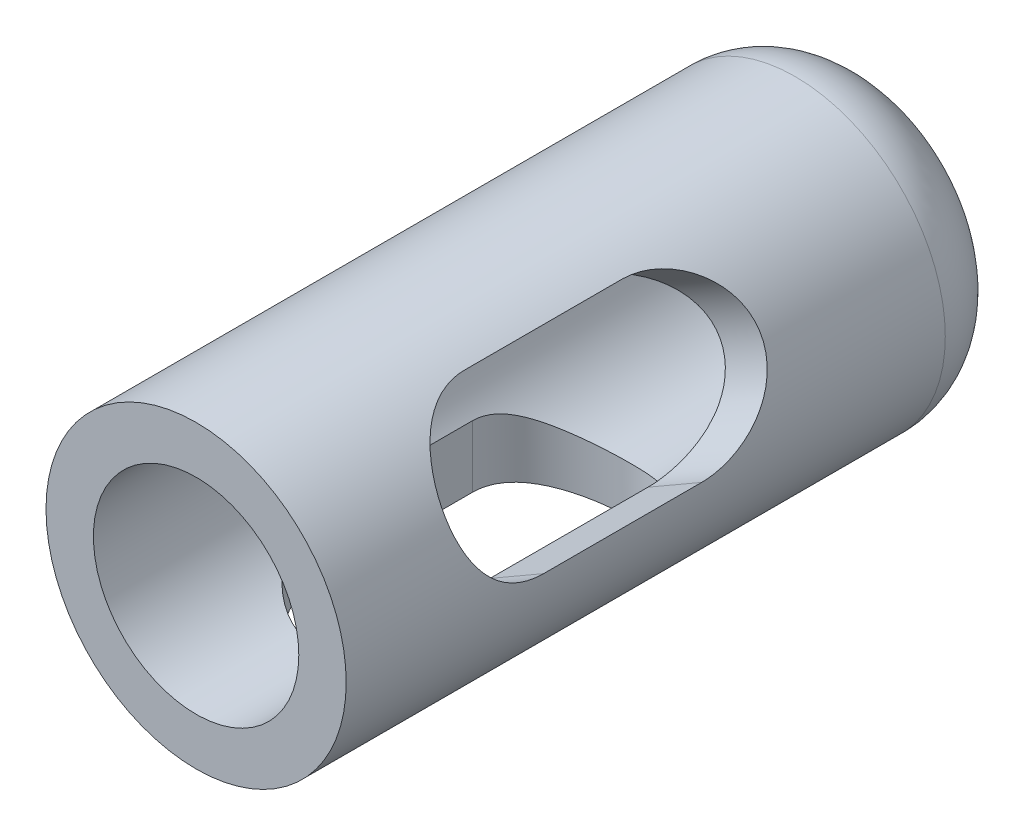
SolidWorks part; units mm, degrees
ref_plane "정면" through (0, 0, 0) normal (0, 0, 1) x (1, 0, 0)
ref_plane "윗면" through (0, 0, 0) normal (0, 1, 0) x (1, 0, 0)
ref_plane "우측면" through (0, 0, 0) normal (1, 0, 0) x (0, 0, -1)
sketch "스케치1" plane through (0, 0, 0) normal (0, 0, 1) x (1, 0, 0)
  circle A0 centre (0, 0) radius 3.8
  circle A1 centre (0, 0) radius 2.6
  dimension "D1" = 7.6
  dimension "D2" = 5.2
extrude "보스-돌출1" add sketch "스케치1" along normal blind 17
sketch "스케치2" plane through (0, 0, 0) normal (0, 1, 0) x (1, 0, 0)
  line L0 (0, -17.6377) -> (0, 0) construction
  line L1 (-2.6, -17) -> (2.6, -17) construction
  line L2 (-2.6, -17) -> (2.6, -17)
  line L3 (-3.8, -17) -> (-2.6, -17)
  line L4 (2.6, -17) -> (3.8, -17)
  line L5 (2.6, -17) -> (3.8, -17)
  line L6 (-3.8, -17) -> (-2.6, -17)
  line L7 (-2, -8) -> (-2, -12)
  line L8 (-2, -12) -> (2, -12)
  line L9 (2, -12) -> (2, -8)
  circle A0 centre (0, -12) radius 2
  circle A1 centre (0, -8) radius 2
  dimension "D1" = 4
  dimension "D3" = 4
  dimension "D2" = 5
  dimension "D4" = 4
extrude "컷-돌출1" cut sketch "스케치2" against normal blind 17 contours L0 A0 A1 L9 | A0 L0 A1 L7 | A1 A0 L9 | L0 L8 A0 A1 | L8 L0 A1 A0 | A1 L7 A0 | A0 L0 L8 | L0 A0 L8 | L0 A1 A0 | A1 L0 A0 region at (-0.8488, 0, 12.8488) region at (0.8488, 0, 12.8488) region at (-0.8488, 0, 11.1512) region at (0.8488, 0, 11.1512) region at (-1.5533, 0, 10) region at (1.5533, 0, 10) region at (-0.8488, 0, 8) region at (0.8488, 0, 8)
sketch "스케치3" plane through (0, 0, 0) normal (0, 0, 1) x (1, 0, 0)
  line L0 (0, 0) -> (0, -1.5583) construction
  line L1 (0, 0) -> (5.1536, 2.9754) construction
  line L2 (0, 0) -> (3.9798, 2.2977)
  dimension "D1" = 120
sketch3d "3D스케치2"
  line L1 (0, 0, 0) -> (5.1536, 2.9754, 0) construction
sketch "스케치4" plane through (0, 0, 0) normal (0, 1, 0) x (1, 0, 0)
  line L0 (0, 0) -> (0, -27.8189) construction
  point P3 (0, 0)
  point P4 (0, -27.8189)
pattern_circular "원형 패턴1" count 2 over 120 about axis through (0, 0, 0) along (0, 0, 1) of "컷-돌출1"
fillet "필렛1" radius 2 1 edges at (3.8, 0, 0)
